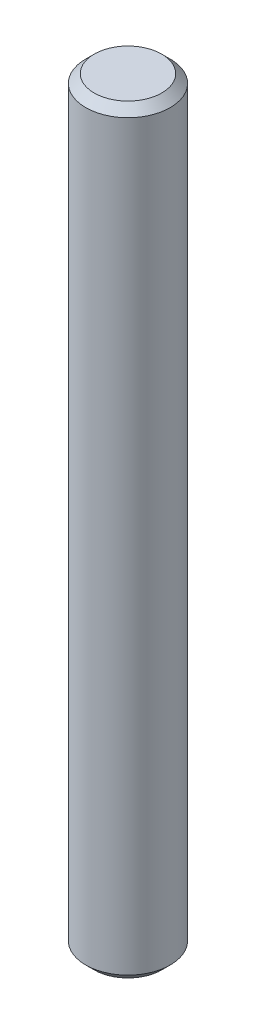
SolidWorks part; units mm, degrees
material "AISI 316 Annealed Stainless Steel Bar (SS)"
ref_plane "Front Plane" through (0, 0, 0) normal (0, 0, 1) x (1, 0, 0)
ref_plane "Top Plane" through (0, 0, 0) normal (0, 1, 0) x (1, 0, 0)
ref_plane "Right Plane" through (0, 0, 0) normal (1, 0, 0) x (0, 0, -1)
sketch "Sketch1" plane through (0, 0, 0) normal (0, 1, 0) x (1, 0, 0)
  circle A0 centre (0, 0) radius 3.175
  dimension "D1" = 6.35
extrude "Boss-Extrude1" add sketch "Sketch1" along normal blind 57.15
chamfer "Chamfer1" distance 0.635 angle 45 2 edges at (0, 0, 3.175) (0, 57.15, 3.175)
